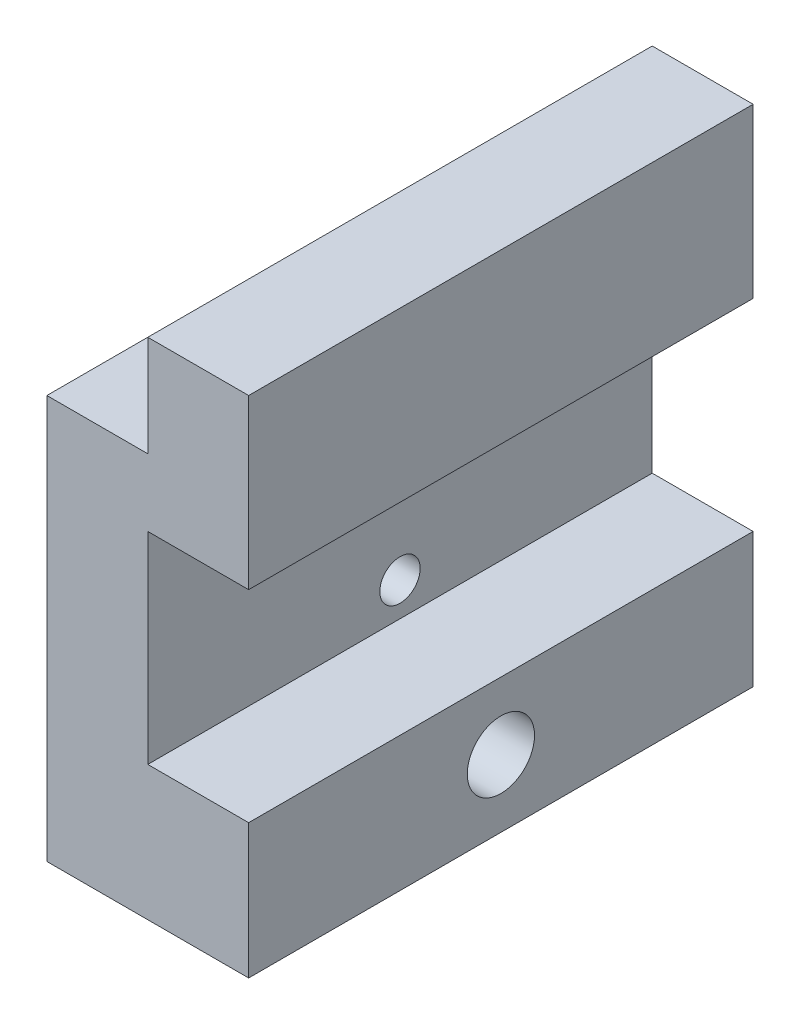
SolidWorks part; units mm, degrees
ref_plane "Front Plane" through (0, 0, 0) normal (0, 0, 1) x (1, 0, 0)
ref_plane "Top Plane" through (0, 0, 0) normal (0, 1, 0) x (1, 0, 0)
ref_plane "Right Plane" through (0, 0, 0) normal (1, 0, 0) x (0, 0, -1)
sketch "Sketch1" plane through (0, 0, 0) normal (0, 0, 1) x (1, 0, 0)
  line L0 (0, 0) -> (68952.629, 0) construction
  line L1 (104.6471, 0) -> (104.6471, 68952.629) construction
  line L2 (104.7021, 60) -> (30, 60) construction
  line L3 (0, 51.7317) -> (0, -68900.8974) construction
  line L4 (30, 0) -> (0, 0)
  line L5 (0, 0) -> (0, 60)
  line L6 (0, 60) -> (15, 60)
  line L7 (30, 60) -> (30, 50)
  line L8 (30, 50) -> (15, 50)
  line L9 (15, 50) -> (15, 20)
  line L10 (15, 20) -> (30, 20)
  line L11 (30, 20) -> (30, 0)
  line L12 (30, 60) -> (30, 75)
  line L13 (30, 75) -> (15, 75)
  line L14 (15, 75) -> (15, 60)
  line L15 (15, 60) -> (-68847.9269, 60) construction
  dimension "D1" = 30
  dimension "D2" = 15
  dimension "D3" = 10
  dimension "D4" = 20
  dimension "D5" = 15
  dimension "D6" = 15
  dimension "D7" = 30
extrude "Boss-Extrude1" add sketch "Sketch1" against normal blind 75
sketch "Sketch2" plane through (30, 0, 0) normal (1, 0, 0) x (0, 0, -1)
  line L0 (37.5, 0) -> (37.5, 20) construction
  line L1 (75, 0) -> (0, 0) construction
  line L2 (75, 20) -> (0, 20) construction
  circle A0 centre (37.5, 10) radius 5
extrude "Cut-Extrude1" cut sketch "Sketch2" against normal blind 50
sketch "Sketch3" plane through (0, 0, 0) normal (-1, 0, 0) x (0, 0, 1)
  line L0 (-37.5, 0) -> (-37.5, 60) construction
  line L1 (-75, 0) -> (0, 0) construction
  line L2 (-75, 60) -> (0, 60) construction
  line L4 (-75, 50) -> (0, 50) construction
  line L5 (0, 60) -> (0, 0) construction
  line L6 (87.5, 50) -> (-162.5, 50) construction
  circle A0 centre (-37.5, 25) radius 3
  dimension "D1" = 25
extrude "Cut-Extrude2" cut sketch "Sketch3" against normal blind 101
